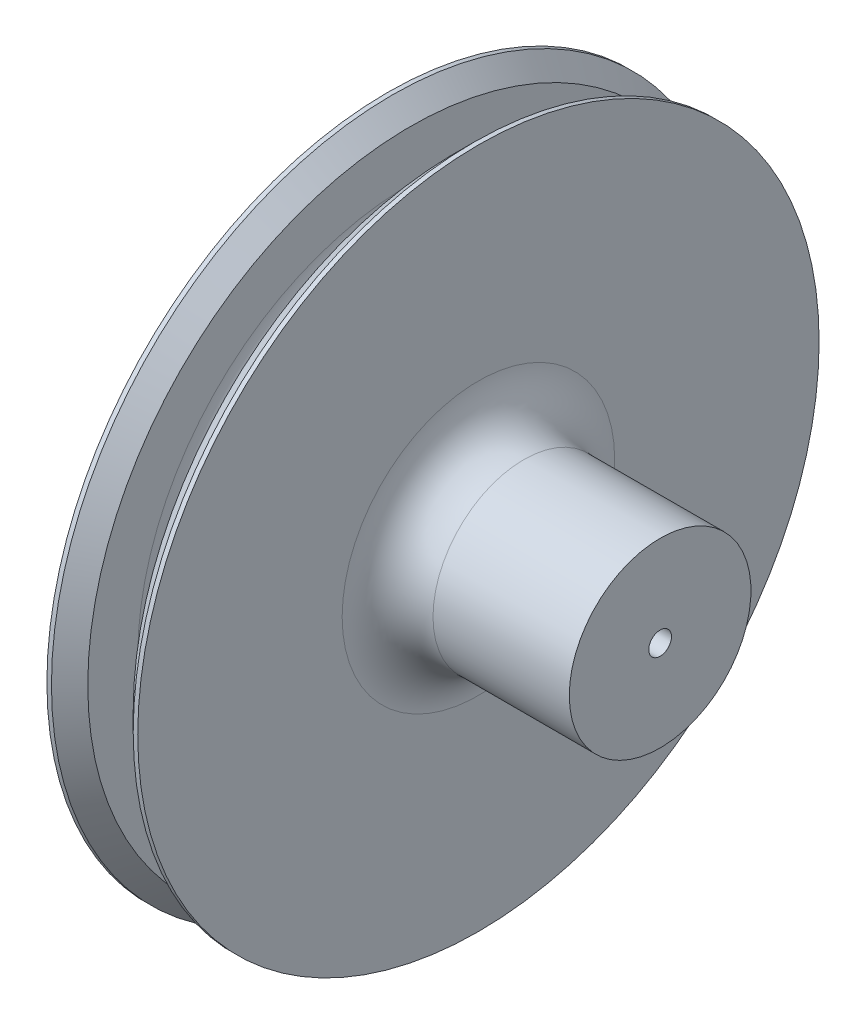
SolidWorks part; units mm, degrees
material "ALUMINUM 6061-T6; 6061-T651"
ref_plane "Front Plane" through (0, 0, 0) normal (0, 0, 1) x (1, 0, 0)
ref_plane "Top Plane" through (0, 0, 0) normal (0, 1, 0) x (1, 0, 0)
ref_plane "Right Plane" through (0, 0, 0) normal (1, 0, 0) x (0, 0, -1)
sketch "Sketch1" plane through (0, 0, 0) normal (0, 0, 1) x (1, 0, 0)
  line L0 (0, 19.05) -> (0, -19.05) construction
  line L3 (-1.5875, -19.05) -> (-1.5875, -23.8125)
  line L4 (1.5875, -19.05) -> (1.5875, -23.8125)
  line L5 (-3.175, -23.8125) -> (-1.5875, -23.8125)
  line L6 (1.5875, -23.8125) -> (3.175, -23.8125)
  line L9 (-3.175, -23.8125) -> (-3.175, 0)
  line L10 (-3.175, 0) -> (3.175, 0)
  line L11 (3.175, 0) -> (3.175, -23.8125)
  arc A1 (1.5875, -19.05) -> (-1.5875, -19.05) centre (0, -19.05) ccw
  circle A2 centre (0, 19.05) radius 1.5875 construction
  circle A3 centre (0, -19.05) radius 1.5875 construction
  dimension "D2" = 1.5875
  dimension "D1" = 38.1
  dimension "D3" = 6.35
  dimension "D4" = 23.8125
revolve "Revolve1" add sketch "Sketch1" angle 360 about L10
sketch "Sketch2" plane through (-3.175, 0, 0) normal (-1, 0, 0) x (0, 0, 1)
  circle A0 centre (0, 0) radius 6.35
  dimension "D1" = 12.7
extrude "Boss-Extrude1" add sketch "Sketch2" along normal blind 3.175 and the other way blind 19.05 contours A0
sketch "Sketch3" plane through (-6.35, 0, 0) normal (-1, 0, 0) x (0, 0, 1)
  circle A0 centre (0, 0) radius 0.7937
  dimension "D1" = 1.5875
extrude "Cut-Extrude1" cut sketch "Sketch3" against normal through all both and the other way through all
fillet "Fillet1" radius 3.175 2 edges at (-3.175, 0, 6.35) (3.175, 0, -6.35)
chamfer "Chamfer1" distance 1.27 angle 45 2 edges at (-1.5875, 0, 23.8125) (1.5875, 0, 23.8125)
